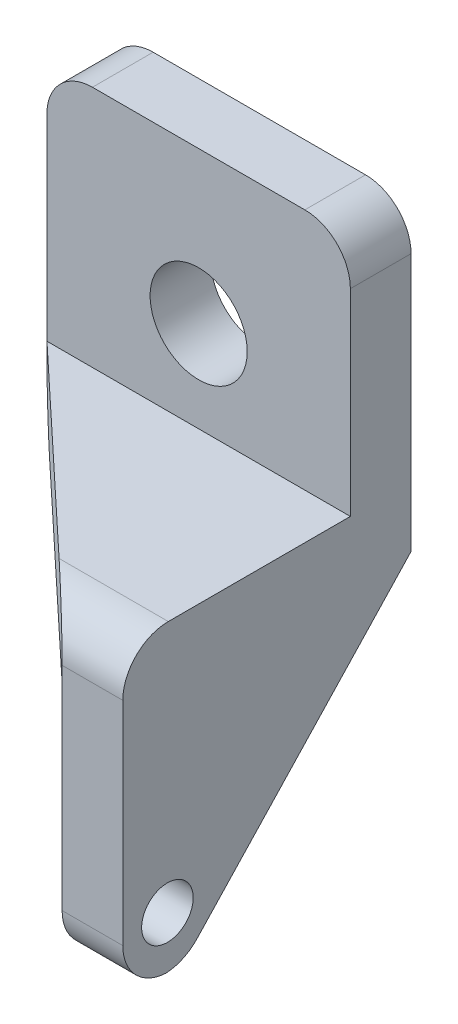
SolidWorks part; units mm, degrees
ref_plane "Front Plane" through (0, 0, 0) normal (0, 0, 1) x (1, 0, 0)
ref_plane "Top Plane" through (0, 0, 0) normal (0, 1, 0) x (1, 0, 0)
ref_plane "Right Plane" through (0, 0, 0) normal (1, 0, 0) x (0, 0, -1)
sketch "Sketch1" plane through (0, 0, 0) normal (0, 0, 1) x (1, 0, 0)
  line L1 (-10, -10) -> (10, -10)
  line L2 (-10, -10) -> (-10, 10)
  line L3 (-10, 10) -> (10, 10)
  line L4 (10, -10) -> (10, 10)
  line L5 (-10, -10) -> (10, 10) construction
  line L6 (-10, 10) -> (10, -10) construction
  circle A0 centre (0, 0) radius 3.2
  point P0 (0, 0)
extrude "Boss-Extrude1" add sketch "Sketch1" along normal blind 4
sketch "Sketch2" plane through (0, 0, 4) normal (0, 0, 1) x (1, 0, 0)
  line L0 (10, -10) -> (10, 10) construction
  line L1 (-10, -10) -> (10, -10)
  line L2 (-10, -10) -> (-10, -6)
  line L3 (-10, -6) -> (10, -6)
  line L4 (10, -10) -> (10, -6)
  dimension "D1" = 4
extrude "Boss-Extrude2" add sketch "Sketch2" along normal blind 15
sketch "Sketch3" plane through (0, -6, 0) normal (0, 1, 0) x (1, 0, 0)
  line L0 (-10, -19) -> (-10, -4)
  line L1 (-10, -4) -> (6, -19)
  line L2 (10, -19) -> (-10, -19) construction
  line L3 (6, -19) -> (-10, -19)
  dimension "D1" = 4
extrude "Cut-Extrude1" cut sketch "Sketch3" against normal blind 15
sketch "Sketch4" plane through (10, 0, 0) normal (1, 0, 0) x (0, 0, -1)
  line L0 (0, -10) -> (-15, -26)
  line L1 (-19, -10) -> (0, -10)
  line L2 (-19, -10) -> (-19, -26)
  line L3 (-19, -26) -> (-15, -26)
  dimension "D2" = 4
extrude "Boss-Extrude3" add sketch "Sketch4" against normal blind 4
sketch "Sketch5" plane through (10, 0, 0) normal (1, 0, 0) x (0, 0, -1)
  circle A0 centre (-16.0591, -22.5875) radius 1.7
  point P2 (-16.0591, -22.5875)
extrude "Cut-Extrude2" cut sketch "Sketch5" against normal blind 4
fillet "Fillet1" radius 3 2 edges at (8, -26, 15) (8, -26, 19)
fillet "Fillet2" radius 3 4 edges at (-10, -10, 2) (-10, 10, 2) (10, 10, 2) (8, -6, 19)
